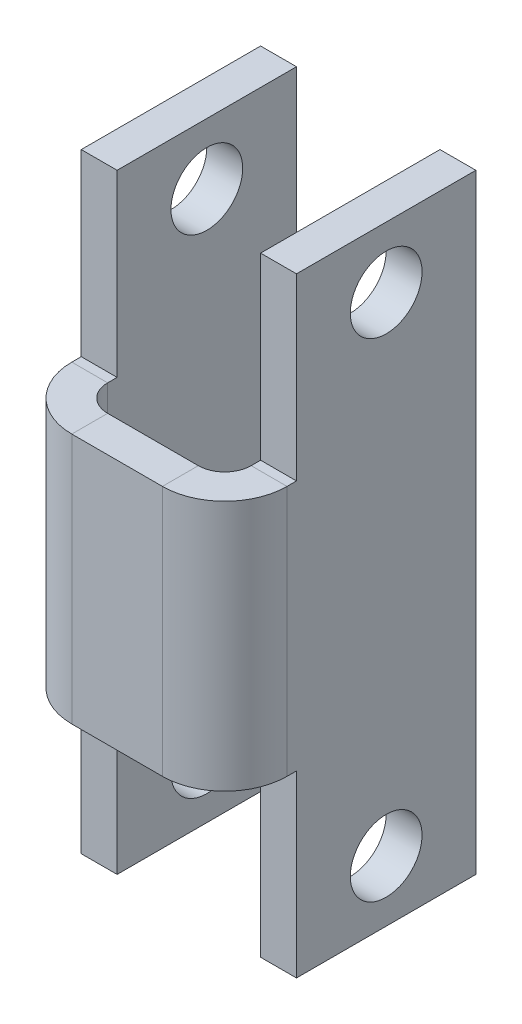
SolidWorks part; units mm, degrees
note: The reader was unsure of these and kept them because the rebuilt part matched: flange length of "Brida de arista1".
ref_plane "Alzado" through (0, 0, 0) normal (0, 0, 1) x (1, 0, 0)
ref_plane "Planta" through (0, 0, 0) normal (0, 1, 0) x (1, 0, 0)
ref_plane "Vista lateral" through (0, 0, 0) normal (1, 0, 0) x (0, 0, -1)
sketch "Croquis1" plane through (0, 0, 0) normal (0, 0, 1) x (1, 0, 0)
  line L1 (0, 0) -> (6, 0)
  line L2 (0, 0) -> (0, 17)
  line L3 (0, 17) -> (6, 17)
  line L4 (6, 0) -> (6, 17)
  dimension "D1" = 6
  dimension "D2" = 17
base flange "Brida base1" sketch "Croquis1" thickness 1 reverse thickness direction no parameters "D1"=0.7366
edge flange "Brida de arista1" sketch "Croquis10" flange profiles "Croquis10", "Croquis11" flange angle 90 flange length 7 flange position material inside bend radius 0.7366 thickness 1 relief rectangular parameters "D6"=10, "D8"=0.5
sketch "Croquis10" plane through (6, 0, -1) normal (1, 0, 0) x (0, -1, 0)
  line L2 (-17, 0) -> (-17, 6)
  line L3 (-17, 6) -> (0, 6)
  line L4 (0, 6) -> (0, 0)
  line L5 (0, 0) -> (-17, 0) construction
  line L6 (0, 0) -> (-17, 0)
sketch "Croquis11" plane through (0, 0, -1) normal (-1, 0, 0) x (0, 1, 0)
  line L0 (17, 0) -> (0, 0) construction
  line L1 (17, 0) -> (0, 0)
  line L2 (0, 0) -> (0, 6)
  line L3 (0, 6) -> (17, 6)
  line L4 (17, 6) -> (17, 0)
bend "Pliegue de arista1" bend radius 0.7366 bend angle 90 parameters "D5"=1
bend "Pliegue de arista2" bend radius 0.7366 bend angle 90 parameters "D5"=2
sketch "Croquis12" plane through (6, 0, 0) normal (1, 0, 0) x (0, 0, -1)
  line L0 (7, 8.5) -> (0, 8.5) construction
  line L1 (0, 17) -> (2, 17)
  line L2 (0, 17) -> (0, 12)
  line L3 (0, 12) -> (2, 12)
  line L4 (2, 17) -> (2, 12)
  line L5 (7, 0) -> (7, 17) construction
  line L6 (0, 0) -> (0, 17) construction
  line L7 (2, 0) -> (2, 5)
  line L8 (0, 5) -> (2, 5)
  line L9 (0, 0) -> (0, 5)
  line L10 (0, 0) -> (2, 0)
  dimension "D1" = 2
  dimension "D2" = 5
extrude "Cortar-Extruir1" cut sketch "Croquis12" against normal blind 10 normal cut yes
sketch "Croquis13" plane through (6, 0, 0) normal (1, 0, 0) x (0, 0, -1)
  line L0 (4.5, 17) -> (4.5, 15.3) construction
  line L1 (7, 17) -> (2, 17) construction
  line L2 (7, 8.5) -> (0, 8.5) construction
  line L3 (7, 0) -> (7, 17) construction
  line L4 (0, 5) -> (0, 12) construction
  circle A0 centre (4.5, 15.3) radius 1
  circle A1 centre (4.5, 1.7) radius 1
  dimension "D2" = 2
  dimension "D1" = 1.7
extrude "Cortar-Extruir2" cut sketch "Croquis13" against normal blind 10 normal cut yes
sketch "Líneas de pliegue1" [suppressed] plane through (0, 0, 0) normal (0, 1, 0) x (1, 0, 0)
sketch "Cuadro delimitador1" [suppressed] plane through (0, 0, 0) normal (0, 1, 0) x (1, 0, 0)
sheet metal parameters "Chapa metálica1" thickness 1 parameters "D1"=0.7366
flat pattern "Chapa desplegada1" [suppressed]
sketch "Líneas de pliegue2" plane through (0, 0, 0) normal (0, 1, 0) x (1, 0, 0)
sketch3d "Cuadro delimitador2" [suppressed]
  line L0 (-6, 17, 0) -> (-6, 0, 0) construction
  line L1 (0, 17, 0) -> (0, 0, 0) construction
  line L2 (-6, 17, 0) -> (0, 17, 0) construction
  line L3 (-6, 0, 0) -> (0, 0, 0) construction
sheet metal parameters "Chapa metálica2" thickness 1 parameters "D1"=0.7366
flat pattern "Chapa desplegada1"
sketch "Líneas de pliegue2" plane through (0, 0, 0) normal (0, 0, 1) x (1, 0, 0)
  line L0 (0.7654, 17) -> (0.7654, 0) construction
  line L1 (5.2346, 0) -> (5.2346, 17) construction
  line L2 (0.7654, 17) -> (0.7654, 0) construction
  line L3 (5.2346, 0) -> (5.2346, 17) construction
sketch3d "Cuadro delimitador2" [suppressed]
  line L0 (11.4692, 17, 0) -> (11.4692, 0, 0) construction
  line L1 (-5.4692, 17, 0) -> (-5.4692, 0, 0) construction
  line L2 (11.4692, 17, 0) -> (-5.4692, 17, 0) construction
  line L3 (11.4692, 0, 0) -> (-5.4692, 0, 0) construction
bend of the flat pattern "Aplanar-<Pliegue de arista1>1"
bend of the flat pattern "Aplanar-<Pliegue de arista2>1"
sheet metal parameters "Chapa metálica3" thickness 1 parameters "D1"=0.7366
flat pattern "Chapa desplegada1"
sketch "Líneas de pliegue2" plane through (0, 0, 0) normal (0, 0, 1) x (1, 0, 0)
  line L0 (0.7654, 12) -> (0.7654, 5) construction
  line L1 (5.2346, 5) -> (5.2346, 12) construction
  line L2 (0.7654, 12) -> (0.7654, 5) construction
  line L3 (5.2346, 5) -> (5.2346, 12) construction
sketch3d "Cuadro delimitador2" [suppressed]
  line L0 (11.4692, 17, 0) -> (11.4692, 0, 0) construction
  line L1 (-5.4692, 17, 0) -> (-5.4692, 0, 0) construction
  line L2 (11.4692, 17, 0) -> (-5.4692, 17, 0) construction
  line L3 (11.4692, 0, 0) -> (-5.4692, 0, 0) construction
bend of the flat pattern "Aplanar-<Pliegue de arista1>1"
bend of the flat pattern "Aplanar-<Pliegue de arista2>1"
sheet metal parameters "Chapa metálica4" thickness 1 parameters "D1"=0.7366
flat pattern "Chapa desplegada1"
sketch "Líneas de pliegue2" plane through (0, 0, 0) normal (0, 0, 1) x (1, 0, 0)
  line L0 (0.7654, 12) -> (0.7654, 5) construction
  line L1 (5.2346, 5) -> (5.2346, 12) construction
  line L2 (0.7654, 12) -> (0.7654, 5) construction
  line L3 (5.2346, 5) -> (5.2346, 12) construction
sketch3d "Cuadro delimitador2" [suppressed]
  line L0 (11.4692, 17, 0) -> (11.4692, 0, 0) construction
  line L1 (-5.4692, 17, 0) -> (-5.4692, 0, 0) construction
  line L2 (11.4692, 17, 0) -> (-5.4692, 17, 0) construction
  line L3 (11.4692, 0, 0) -> (-5.4692, 0, 0) construction
bend of the flat pattern "Aplanar-<Pliegue de arista1>1"
bend of the flat pattern "Aplanar-<Pliegue de arista2>1"
